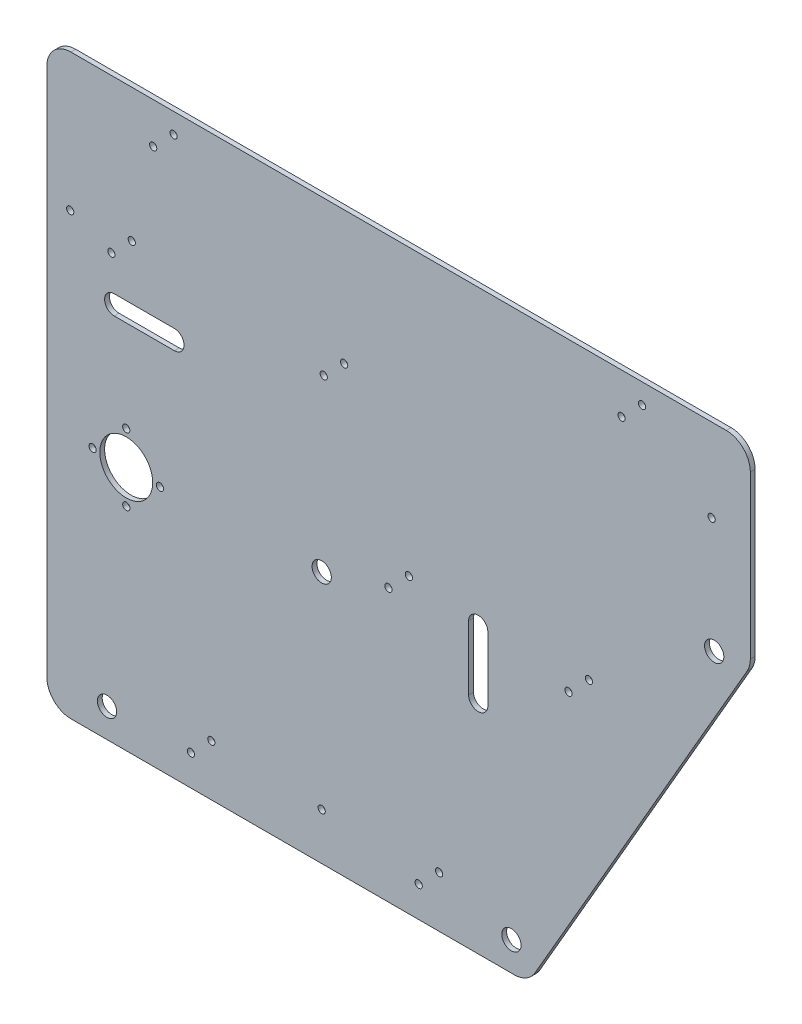
SolidWorks part; units mm, degrees
ref_plane "Front Plane" through (0, 0, 0) normal (0, 0, 1) x (1, 0, 0)
ref_plane "Top Plane" through (0, 0, 0) normal (0, 1, 0) x (1, 0, 0)
ref_plane "Right Plane" through (0, 0, 0) normal (1, 0, 0) x (0, 0, -1)
sketch "Sketch1" plane through (0, 0, 0) normal (0, 0, 1) x (1, 0, 0)
  line L0 (100, 80) -> (192.376, 80)
  line L1 (-100, -80) -> (100, -80)
  line L2 (-100, -80) -> (-100, 80)
  line L3 (-100, 80) -> (100, 80)
  line L4 (100, -80) -> (100, 80)
  line L5 (-100, -80) -> (100, 80) construction
  line L6 (-100, 80) -> (100, -80) construction
  line L7 (192.376, 80) -> (100, -80)
  line L8 (100, 80) -> (100, -80)
  line L10 (-100, 80) -> (192.376, 80)
  line L11 (-100, 80) -> (-100, 110)
  line L12 (-100, 110) -> (192.376, 110)
  line L13 (192.376, 80) -> (192.376, 110)
  point P0 (0, 0)
  dimension "D1" = 160
  dimension "D2" = 200
  dimension "D3" = 30
  dimension "D4" = 30
extrude "Boss-Extrude1" add sketch "Sketch1" along normal blind 2 contours L1 L4 L3 L2 | L7 L0 L4 | L11 L10 L13 L12 region at (0, 0, 0) region at (130.792, 26.6667, 0)
sketch "Sketch2" plane through (0, 0, 2) normal (0, 0, 1) x (1, 0, 0)
  line L0 (-100, -80) -> (100, -80) construction
  line L1 (192.376, 80) -> (100, -80) construction
  line L2 (79.2904, 11.2418) -> (79.2904, 37.9086) construction
  line L3 (-100, -80) -> (-100, 110) construction
  line L4 (-72, 78) -> (-47, 78) construction
  line L7 (-100, 110) -> (192.376, 110) construction
  line L8 (75.2904, 11.2418) -> (75.2904, 37.9086)
  line L9 (-72, 82) -> (-47, 82)
  line L10 (-72, 74) -> (-47, 74)
  line L11 (-100, -80) -> (-100, 110) construction
  line L12 (83.2904, 11.2418) -> (83.2904, 37.9086)
  circle A0 centre (93.0718, -68) radius 4
  circle A1 centre (177.3649, 78) radius 4
  circle A2 centre (-67, 22) radius 11
  circle A3 centre (-75, -68) radius 4
  circle A4 centre (-53, 22) radius 1.5
  circle A5 centre (-67, 36) radius 1.5
  circle A6 centre (-81, 22) radius 1.5
  circle A7 centre (-67, 8) radius 1.5
  circle A11 centre (54.5495, -67.2426) radius 1.5
  circle A12 centre (63.0348, -58.7574) radius 1.5
  circle A13 centre (14.2259, -60.5) radius 1.5
  circle A14 centre (-40.1271, -67.2426) radius 1.5
  circle A15 centre (-31.6419, -58.7574) radius 1.5
  circle A16 centre (-90.2956, 102.8814) radius 1.5
  circle A17 centre (-73.1863, 96.1388) radius 1.5
  circle A18 centre (-64.701, 104.6241) radius 1.5
  circle A19 centre (15.0782, 96.1388) radius 1.5
  circle A20 centre (23.5635, 104.6241) radius 1.5
  circle A21 centre (41.9695, 33.1388) radius 1.5
  circle A22 centre (50.4548, 41.6241) radius 1.5
  circle A23 centre (-39.813, 33.1388) radius 1.5 construction
  circle A24 centre (-31.3277, 41.6241) radius 1.5 construction
  circle A25 centre (116.8113, 33.1388) radius 1.5
  circle A26 centre (125.2966, 41.6241) radius 1.5
  circle A27 centre (79.2904, 25) radius 4 construction
  circle A28 centre (14.2259, 25) radius 4
  arc A29 (-72, 82) -> (-72, 74) centre (-72, 78) ccw
  arc A30 (-47, 74) -> (-47, 82) centre (-47, 78) ccw
  circle A31 centre (176.3056, 125.4889) radius 1.5
  arc A32 (75.2904, 11.2418) -> (83.2904, 11.2418) centre (79.2904, 11.2418) ccw
  arc A33 (83.2904, 37.9086) -> (75.2904, 37.9086) centre (79.2904, 37.9086) ccw
  circle A34 centre (-55.8147, 143.1388) radius 1.5
  circle A35 centre (-47.3294, 151.6241) radius 1.5
  circle A36 centre (138.8916, 143.1388) radius 1.5
  circle A37 centre (147.3769, 151.6241) radius 1.5
  point P26 (-59.5, 78)
  point P87 (79.2904, 24.5752)
  dimension "D3" = 8
  dimension "D4" = 8
  dimension "D9" = 22
  dimension "D10" = 8
  dimension "D12" = 3
  dimension "D13" = 3
  dimension "D14" = 3
  dimension "D15" = 3
  dimension "D16" = 14
  dimension "D20" = 8
  dimension "D22" = 4
  dimension "D25" = 3
  dimension "D26" = 3
  dimension "D29" = 8
  dimension "D28" = 3
  dimension "D1" = 12
  dimension "D2" = 12
  dimension "D5" = 32
  dimension "D6" = 12
  dimension "D7" = 88
  dimension "D8" = 33
  dimension "D11" = 12
  dimension "D17" = 14
  dimension "D18" = 14
  dimension "D19" = 14
  dimension "D21" = 85
  dimension "D23" = 28
  dimension "D24" = 25
  dimension "D27" = 25
  dimension "D30" = 8
extrude "Cut-Extrude1" cut sketch "Sketch2" against normal blind 3
sketch "Sketch4" plane through (0, 0, 2) normal (0, 0, 1) x (1, 0, 0)
  line L0 (192.376, 80) -> (192.376, 110) construction
  line L1 (-100, 110) -> (192.376, 110)
  line L2 (-100, 110) -> (-100, 160)
  line L3 (-100, 160) -> (192.376, 160)
  line L4 (192.376, 110) -> (192.376, 160)
  dimension "D1" = 50
extrude "Boss-Extrude2" add sketch "Sketch4" against normal blind 2
fillet "Fillet1" radius 10 5 edges at (192.376, 160, 1) (192.376, 80, 1) (100, -80, 1) (-100, -80, 1) (-100, 160, 1)
sketch "Sketch5" plane through (0, 0, 2) normal (0, 0, 1) x (1, 0, 0)
  circle A2 centre (-55.8147, 143.1388) radius 1.5
  circle A3 centre (-47.3294, 151.6241) radius 1.5
  circle A4 centre (138.8916, 143.1388) radius 1.5
  circle A5 centre (147.3769, 151.6241) radius 1.5
  circle A6 centre (176.3056, 125.4889) radius 1.5
  dimension "D1" = 3
extrude "Cut-Extrude2" cut sketch "Sketch5" against normal blind 11
